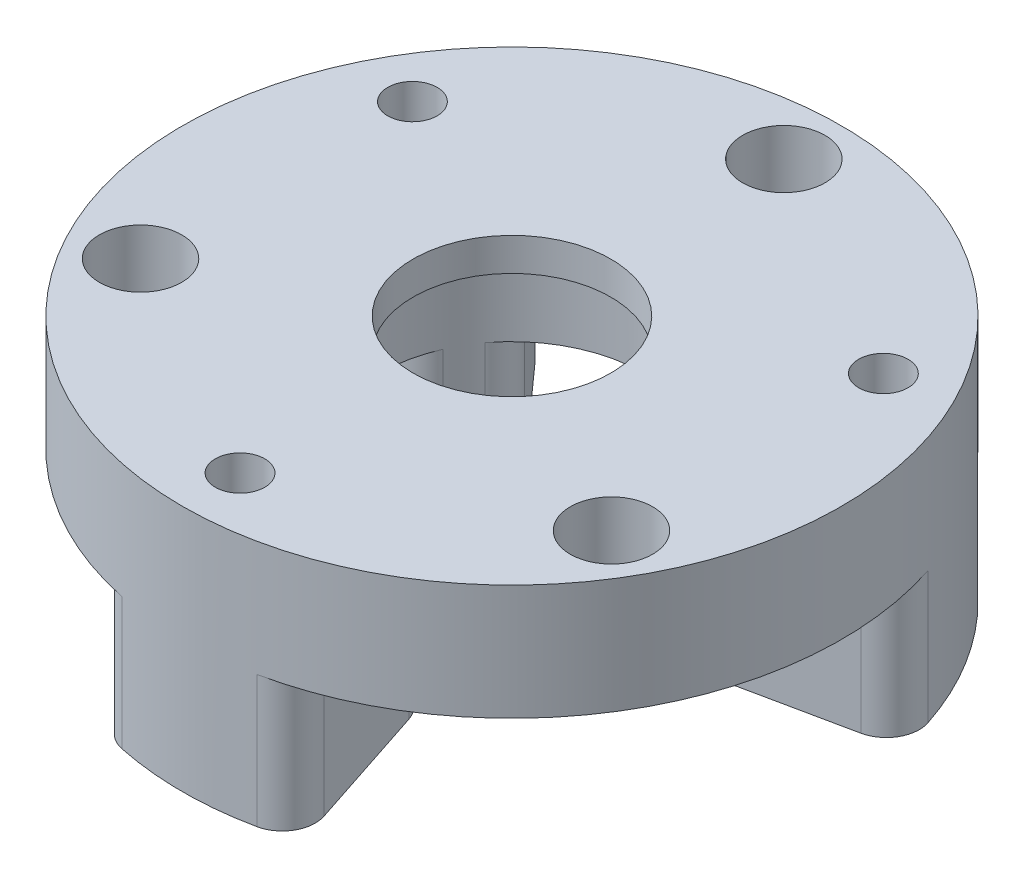
SolidWorks part; units mm, degrees
ref_plane "Front Plane" through (0, 0, 0) normal (0, 0, 1) x (1, 0, 0)
ref_plane "Top Plane" through (0, 0, 0) normal (0, 1, 0) x (1, 0, 0)
ref_plane "Right Plane" through (0, 0, 0) normal (1, 0, 0) x (0, 0, -1)
sketch "Sketch1" plane through (0, 0, 0) normal (0, 1, 0) x (1, 0, 0)
  circle A0 centre (0, 0) radius 20
  circle A1 centre (0, 0) radius 8
  dimension "D1" = 40
  dimension "D2" = 16
extrude "Boss-Extrude1" add sketch "Sketch1" along normal blind 8 contours A0 A1 region at (-19.4343, 0, 0)
sketch "Sketch2" plane through (0, 8, 0) normal (0, 1, 0) x (1, 0, 0)
  circle A0 centre (0, 0) radius 20
  circle A1 centre (0, 0) radius 20
  circle A2 centre (0, 0) radius 20
  circle M3 centre (0, 0) radius 8
  circle M4 centre (0, 0) radius 20
  dimension "D2" = 40
  dimension "D1" = 0
extrude "Boss-Extrude2" add sketch "Sketch2" along normal blind 7 contours M4 M3 | A0 M4 region at (-19.4343, 8, 0)
sketch "Sketch3" plane through (0, 15, 0) normal (0, 1, 0) x (1, 0, 0)
  circle A0 centre (0, 0) radius 8 construction
  circle A1 centre (0, 0) radius 8
  circle A2 centre (0, 0) radius 6
  dimension "D1" = 12
extrude "Boss-Extrude3" add sketch "Sketch3" against normal blind 2
sketch "Sketch4" plane through (0, 15, 0) normal (0, 1, 0) x (1, 0, 0)
  circle A0 centre (0, 0) radius 16.5 construction
  circle A1 centre (0, 16.5) radius 2.5
  circle A2 centre (14.2894, -8.25) radius 2.5
  circle A3 centre (-14.2894, -8.25) radius 2.5
  circle A4 centre (0, -16.5) radius 1.5
  circle A5 centre (-14.2894, 8.25) radius 1.5
  circle A6 centre (0, 0) radius 16.5 construction
  circle A7 centre (14.2894, 8.25) radius 1.5
  circle A8 centre (0, 0) radius 16.5 construction
  point P12 (0, 0)
  point P20 (0, 0)
  dimension "D1" = 33
  dimension "D2" = 5
  dimension "D4" = 3
  dimension "D3" = 3
  dimension "D5" = 3
extrude "Cut-Extrude1" cut sketch "Sketch4" against normal through all
sketch "Sketch5" plane through (0, 0, 0) normal (0, -1, 0) x (1, 0, 0)
  line L0 (-2.4973, 7.6002) -> (-6.2433, 19.0006)
  line L1 (0, 8) -> (0, 26.8969) construction
  line L2 (2.4973, 7.6002) -> (6.2433, 19.0006)
  line L3 (6.2433, 19.0006) -> (8.3676, 25.4658) construction
  line L4 (-6.2433, 19.0006) -> (-8.3676, 25.4658) construction
  line L5 (0, 0) -> (-2.4973, 7.6002) construction
  line L6 (0, 0) -> (0, 8) construction
  line L7 (0, 0) -> (2.4973, 7.6002) construction
  line L8 (0, 0) -> (-29.1337, -6.0918)
  circle A0 centre (-14.2894, 8.25) radius 2.5 construction
  circle A1 centre (-14.2894, 8.25) radius 2.5
  arc A2 (-19.9656, -1.1724) -> (-3.8391, 11.6838) centre (-14.2894, 8.25) ccw construction
  circle A3 centre (0, 0) radius 8 construction
  circle A4 centre (0, 0) radius 20 construction
  arc A5 (2.4973, 7.6002) -> (-2.4973, 7.6002) centre (0, 0) ccw
  arc A6 (6.2433, 19.0006) -> (-6.2433, 19.0006) centre (0, 0) ccw
  arc A7 (-7.9648, -0.7499) -> (2.4973, 7.6002) centre (0, 0) ccw
  arc A8 (-19.9656, -1.1724) -> (6.2433, 19.0006) centre (0, 0) ccw
  arc A9 (-3.3329, 7.2727) -> (-7.9648, -0.7499) centre (0, 0) ccw
  arc A10 (-2.4973, 7.6002) -> (-3.3329, 7.2727) centre (0, 0) ccw
  arc A11 (-3.8391, 11.6838) -> (-8.9675, 17.8769) centre (-14.2894, 8.25) ccw construction
  arc A12 (-6.2433, 19.0006) -> (-8.9675, 17.8769) centre (0, 0) ccw
  arc A13 (-8.9675, 17.8769) -> (-19.9656, -1.1724) centre (0, 0) ccw
  arc A14 (-8.9675, 17.8769) -> (-19.9656, -1.1724) centre (-14.2894, 8.25) ccw construction
  circle M7 centre (-14.2894, 8.25) radius 2.5
  circle M10 centre (0, 0) radius 8
  circle M11 centre (0, 0) radius 20
  dimension "D1" = 22
extrude "Cut-Extrude2" cut sketch "Sketch5" against normal blind 8 contours L8 L0 M10 M11 M7 region at (-11.5341, 0, 6.6592)
pattern_circular "CirPattern1" count 3 over 360 about axis through (0, 8, 0) along (0, -1, 0) of "Cut-Extrude2" reverse direction yes
fillet "Fillet1" radius 2 12 edges at (-6.2433, 4, 19.0006) (-7.8306, 4, -1.6374) (-19.5766, 4, -4.0934) (-13.3333, 4, -14.9071) (-5.3333, 4, -5.9628) (5.3333, 4, -5.9628) (13.3333, 4, -14.9071) (19.5766, 4, -4.0934) (7.8306, 4, -1.6374) (2.4973, 4, 7.6002) (6.2433, 4, 19.0006) (-2.4973, 4, 7.6002)
